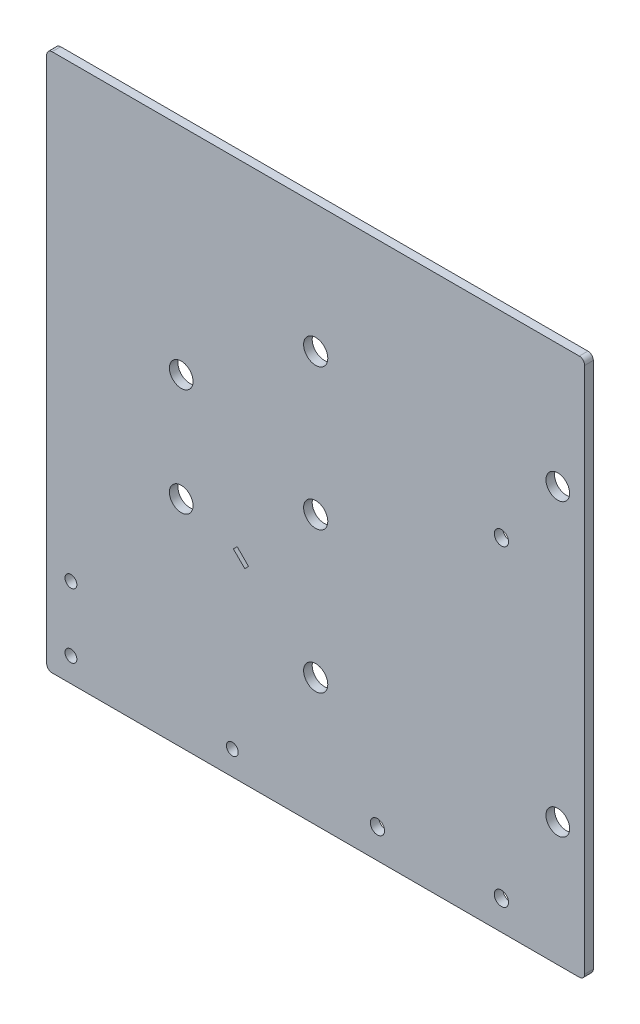
SolidWorks part; units mm, degrees
material "FR4_stuffedProtoboard"
ref_plane "Front Plane" through (0, 0, 0) normal (0, 0, 1) x (1, 0, 0)
ref_plane "Top Plane" through (0, 0, 0) normal (0, 1, 0) x (1, 0, 0)
ref_plane "Right Plane" through (0, 0, 0) normal (1, 0, 0) x (0, 0, -1)
sketch "Sketch1" plane through (0, 0, 0) normal (0, 0, 1) x (1, 0, 0)
  line L1 (-50, -50) -> (50, -50)
  line L2 (-50, -50) -> (-50, 50)
  line L3 (-50, 50) -> (50, 50)
  line L4 (50, -50) -> (50, 50)
  line L5 (-50, -50) -> (50, 50) construction
  line L6 (-50, 50) -> (50, -50) construction
  dimension "D1" = 100
extrude "Boss-Extrude1" add sketch "Sketch1" along normal blind 1.6
sketch "Sketch2" [suppressed] plane through (0, 0, 1.6) normal (0, 0, 1) x (1, 0, 0)
  circle A0 centre (0, 0) radius 50
  line M2 (50, -50) -> (50, 50)
  line M3 (50, 50) -> (-50, 50)
  line M4 (-50, 50) -> (-50, -50)
  line M5 (-50, -50) -> (50, -50)
  dimension "D1" = 100
extrude "Cut-Extrude1" [suppressed] cut sketch "Sketch2" against normal blind 1.6 contours A0 M3 M4 | A0 M4 M5 | A0 M5 M2 | A0 M2 M3
sketch "Sketch3" plane through (0, 0, 1.6) normal (0, 0, -1) x (-1, 0, 0)
  line L0 (-40, -22) -> (-50, -22) construction
  line L1 (-40, -32) -> (-40, -22) construction
  line L2 (-50, -32) -> (-40, -32) construction
  line L3 (-50, -22) -> (-50, -32) construction
  line L4 (-40, -22) -> (-50, -22)
  line L5 (-40, -32) -> (-40, -22)
  line L6 (-50, -32) -> (-40, -32)
  line L7 (-50, -22) -> (-50, -32)
  line L8 (-40, 22) -> (-40, 32) construction
  line L9 (-40, 32) -> (-50, 32) construction
  line L10 (-50, 32) -> (-50, 22) construction
  line L11 (-50, 22) -> (-40, 22) construction
  line L12 (-40, 22) -> (-40, 32)
  line L13 (-40, 32) -> (-50, 32)
  line L14 (-50, 32) -> (-50, 22)
  line L15 (-50, 22) -> (-40, 22)
  line L16 (5, -22) -> (-5, -22) construction
  line L17 (5, -32) -> (5, -22) construction
  line L18 (-5, -32) -> (5, -32) construction
  line L19 (-5, -22) -> (-5, -32) construction
  line L20 (5, -22) -> (-5, -22)
  line L21 (5, -32) -> (5, -22)
  line L22 (-5, -32) -> (5, -32)
  line L23 (-5, -22) -> (-5, -32)
  line L24 (5, 22) -> (5, 32) construction
  line L25 (5, 32) -> (-5, 32) construction
  line L26 (-5, 32) -> (-5, 22) construction
  line L27 (-5, 22) -> (5, 22) construction
  line L28 (5, 22) -> (5, 32)
  line L29 (5, 32) -> (-5, 32)
  line L30 (-5, 32) -> (-5, 22)
  line L31 (-5, 22) -> (5, 22)
  line L32 (17, 25) -> (45, 25) construction
  line L33 (45, 25) -> (45, -25) construction
  line L34 (17, -25) -> (45, -25) construction
  line L35 (17, 25) -> (17, -25) construction
  line L36 (17, 25) -> (45, 25)
  line L37 (45, 25) -> (45, -25)
  line L38 (17, -25) -> (45, -25)
  line L39 (17, 25) -> (17, -25)
  circle A0 centre (0, 26.25) radius 2.2479 construction
  circle A2 centre (0, 26.25) radius 2.2479
  circle A3 centre (0, 0) radius 2.2479
  circle A4 centre (-34.525, -44.525) radius 1.325 construction
  circle A6 centre (-34.525, -44.525) radius 1.325
  circle A8 centre (0, -26.25) radius 2.2479 construction
  circle A9 centre (0, -26.25) radius 2.2479
  circle A11 centre (-45, -27) radius 2.2
  circle A13 centre (-45, 27) radius 2.2
  circle A14 centre (-34.525, 13.525) radius 1.325 construction
  circle A15 centre (-34.525, 13.525) radius 1.325
  circle A16 centre (15.5, -45.5) radius 1.1 construction
  circle A17 centre (15.5, -45.5) radius 1.1
  circle A18 centre (45.5, -45.5) radius 1.1 construction
  circle A19 centre (45.5, -45.5) radius 1.1
  circle A20 centre (45.5, -33.5) radius 1.1 construction
  circle A21 centre (45.5, -33.5) radius 1.1
  circle A22 centre (-11.475, -44.525) radius 1.325 construction
  circle A23 centre (-11.475, -44.525) radius 1.325
  circle A24 centre (25, -10) radius 2.2 construction
  circle A25 centre (25, -10) radius 2.2
  circle A26 centre (25, 10) radius 2.2 construction
  circle A27 centre (25, 10) radius 2.2
  circle A28 centre (-45, 27) radius 2.2 construction
  circle A29 centre (-45, 27) radius 2.2
  circle A30 centre (-45, -27) radius 2.2 construction
  circle A31 centre (-45, -27) radius 2.2
  dimension "D1" = 4.4958
extrude "Cut-Extrude2" cut sketch "Sketch3" along normal through all contours A13 | A11 | A2 | A9 | A3 | A15 | A6 | A23 | A27 | A25 | A17 | A21 | A19 region at (0, 26.25, 1.6) region at (0, 0, 1.6) region at (34.525, -44.525, 1.6) region at (0, -26.25, 1.6) region at (45, -27, 1.6) region at (45, 27, 1.6) region at (34.525, 13.525, 1.6) region at (-15.5, -45.5, 1.6) region at (-45.5, -45.5, 1.6) region at (-45.5, -33.5, 1.6) region at (11.475, -44.525, 1.6) region at (-25, -10, 1.6) region at (-25, 10, 1.6)
sketch "Sketch4" plane through (0, 0, 1.6) normal (0, 0, 1) x (1, 0, 0)
  line L0 (38, -44.25) -> (38, -18.925) construction
  line L5 (38, -44.25) -> (38, -18.925)
  line L6 (11.75, -48) -> (34.25, -48) construction
  line L7 (11.75, -48) -> (34.25, -48)
  line L8 (8, -44.25) -> (8, 13.25) construction
  line L9 (8, -44.25) -> (8, 13.25)
  line L11 (33, -3) -> (33, -48) construction
  line L13 (34.25, 17) -> (11.75, 17)
  line L14 (38, 13.25) -> (38, -18.925)
  line L15 (-48, -48) -> (-13, -48) construction
  line L16 (-48, -48) -> (-13, -48)
  line L17 (-48, -31) -> (-48, -48) construction
  line L18 (-48, -31) -> (-48, -48)
  line L19 (-13, -40.5) -> (-13, -32.5) construction
  line L20 (-13, -40.5) -> (-13, -32.5)
  line L21 (-13, -48) -> (-13, -40.5) construction
  line L22 (-13, -48) -> (-13, -40.5)
  line L23 (-13, -32.5) -> (-13, -31) construction
  line L24 (-13, -32.5) -> (-13, -31)
  line L25 (-13, -31) -> (-48, -31) construction
  line L26 (-13, -31) -> (-48, -31)
  line L27 (-20, -34) -> (-20, -48) construction
  arc A0 (34.25, -48) -> (38, -44.25) centre (34.25, -44.25) ccw construction
  arc A1 (34.25, -48) -> (38, -44.25) centre (34.25, -44.25) ccw
  arc A2 (8, -44.25) -> (11.75, -48) centre (11.75, -44.25) ccw construction
  arc A3 (8, -44.25) -> (11.75, -48) centre (11.75, -44.25) ccw
  arc A4 (11.75, 17) -> (8, 13.25) centre (11.75, 13.25) ccw construction
  arc A5 (11.75, 17) -> (8, 13.25) centre (11.75, 13.25) ccw
  arc A6 (38, 13.25) -> (34.25, 17) centre (34.25, 13.25) ccw construction
  arc A7 (38, 13.25) -> (34.25, 17) centre (34.25, 13.25) ccw
  text T0 "Raspberry Pi Zero W" font "Century Gothic" height 2
  text T1 "Atheros" font "Century Gothic" height 2
  dimension "D1" = 5
  dimension "D2" = 20
  dimension "D3" = 3
  dimension "D4" = 7
fillet "Fillet1" radius 1 4 edges at (-50, -50, 0.8) (-50, 50, 0.8) (50, -50, 0.8) (50, 50, 0.8)
sketch "Sketch5" plane through (0, 0, 0) normal (0, 0, -1) x (-1, 0, 0)
  line L0 (-10, -29.25) -> (-10, -18.6698) construction
  line L5 (10, -18.6698) -> (10, -29.25) construction
  line L6 (-10, -29.25) -> (-10, -18.6698)
  line L7 (10, -18.6698) -> (10, -29.25)
  line L8 (-10, 18.6698) -> (-10, 29.25) construction
  line L9 (7, -32.25) -> (-7, -32.25) construction
  line L10 (-10, 18.6698) -> (-10, 29.25)
  line L11 (7, -32.25) -> (-7, -32.25)
  line L12 (-7, 32.25) -> (7, 32.25) construction
  line L13 (10, 29.25) -> (10, 18.6698) construction
  line L14 (-7, 32.25) -> (7, 32.25)
  line L15 (10, 29.25) -> (10, 18.6698)
  line L16 (12.477, -14.5984) -> (14.5987, -12.4775)
  line L17 (14.5987, -12.4775) -> (15.3057, -13.1847)
  line L18 (15.3057, -13.1847) -> (13.184, -15.3057)
  line L19 (13.184, -15.3057) -> (12.477, -14.5984)
  line L20 (14.2449, -14.2452) -> (13.0417, -13.0416) construction
  arc A0 (-10, -18.6698) -> (-11.2857, -16.2079) centre (-13, -18.6698) ccw construction
  arc A1 (10.9426, -16.4865) -> (10, -18.6698) centre (13, -18.6698) ccw construction
  arc A2 (16.3713, -11.0473) -> (11.2857, 16.2079) centre (0, 0) ccw construction
  arc A3 (-11.2857, 16.2079) -> (-11.2857, -16.2079) centre (0, 0) ccw construction
  arc A4 (-10, -18.6698) -> (-11.2857, -16.2079) centre (-13, -18.6698) ccw
  arc A5 (10.9426, -16.4865) -> (10, -18.6698) centre (13, -18.6698) ccw
  arc A6 (16.3713, -11.0473) -> (11.2857, 16.2079) centre (0, 0) ccw
  arc A7 (-11.2857, 16.2079) -> (-11.2857, -16.2079) centre (0, 0) ccw
  arc A8 (-7, 32.25) -> (-10, 29.25) centre (-7, 29.25) ccw construction
  arc A9 (-11.2857, 16.2079) -> (-10, 18.6698) centre (-13, 18.6698) ccw construction
  arc A10 (-10, -29.25) -> (-7, -32.25) centre (-7, -29.25) ccw construction
  arc A11 (-7, 32.25) -> (-10, 29.25) centre (-7, 29.25) ccw
  arc A12 (-11.2857, 16.2079) -> (-10, 18.6698) centre (-13, 18.6698) ccw
  arc A13 (-10, -29.25) -> (-7, -32.25) centre (-7, -29.25) ccw
  arc A14 (7, -32.25) -> (10, -29.25) centre (7, -29.25) ccw construction
  arc A15 (7, -32.25) -> (10, -29.25) centre (7, -29.25) ccw
  arc A16 (10, 29.25) -> (7, 32.25) centre (7, 29.25) ccw construction
  arc A17 (10, 18.6698) -> (11.2857, 16.2079) centre (13, 18.6698) ccw construction
  arc A18 (10, 29.25) -> (7, 32.25) centre (7, 29.25) ccw
  arc A19 (10, 18.6698) -> (11.2857, 16.2079) centre (13, 18.6698) ccw
  spline S0 degree 3 poles (634.1084, 1871.413) (-1139.8031, -1749.4806) (1542.6668, 1392.446) (-1751.9176, -928.58) knots -42.614825 -42.614825 -42.614825 -42.614825 42.920988 42.920988 42.920988 42.920988 only from (10.9426, -16.4865) to (13.3154, -13.3154) construction
  spline S1 degree 3 poles (928.9937, 1751.4523) (-1395.227, -1538.0404) (1753.4832, 1130.7906) (-1875.7552, -620.724) knots -43.801106 -43.801106 -43.801106 -43.801106 45.540576 45.540576 45.540576 45.540576 only from (13.3154, -13.3154) to (16.3728, -11.0484) construction
  spline S2 degree 3 poles (10.9426, -16.4865) (11.8404, -15.5148) (12.6369, -14.4512) (13.3154, -13.3154) knots 0 0 0 0 1 1 1 1
  spline S3 degree 3 poles (13.3154, -13.3154) (14.4071, -12.6638) (15.4319, -11.9033) (16.3728, -11.0484) knots 0 0 0 0 1 1 1 1
  dimension "D1" = 1
  dimension "D2" = 3
extrude "Cut-Extrude4" cut sketch "Sketch5" against normal through all contours L18 L19 L16 L17
